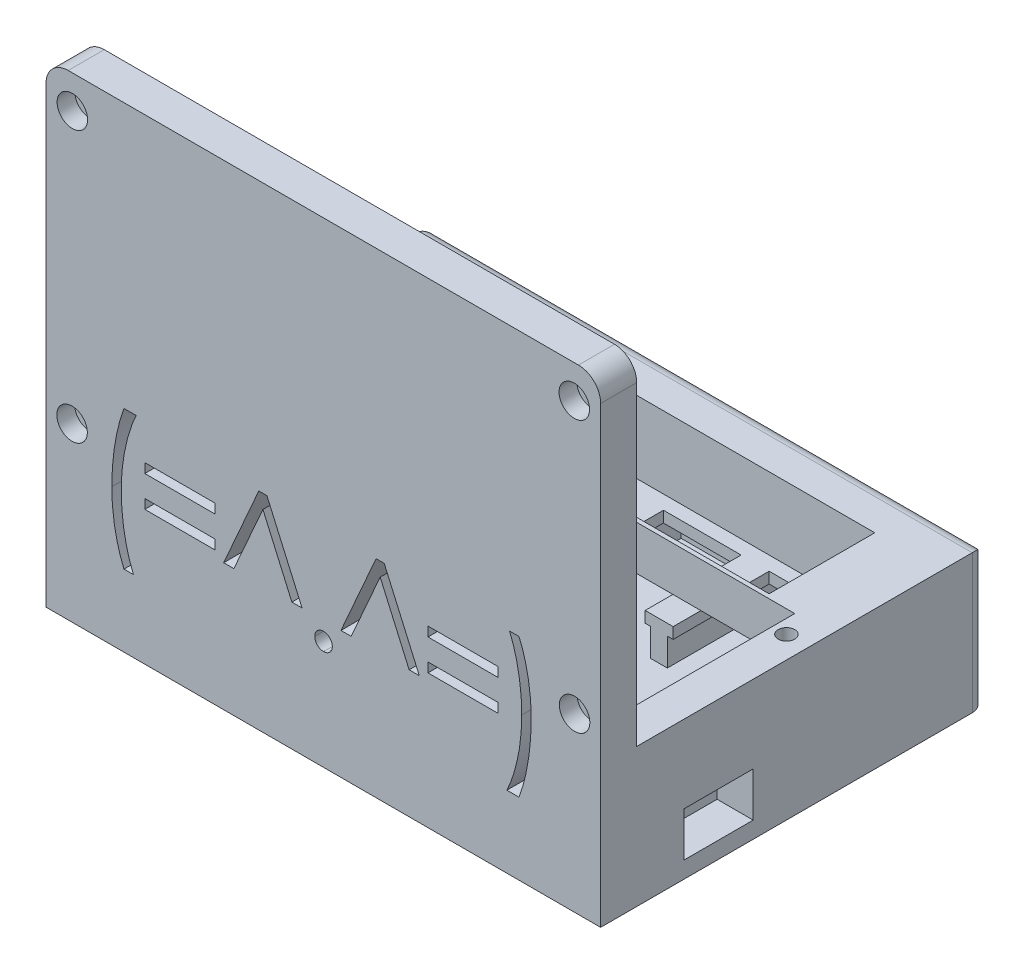
SolidWorks part; units mm, degrees
note: The reader was unsure of these and kept them because the rebuilt part matched: shared geometry of "Sketch32<3>".
ref_plane "Front Plane" through (0, 0, 0) normal (0, 0, 1) x (1, 0, 0)
ref_plane "Top Plane" through (0, 0, 0) normal (0, 1, 0) x (1, 0, 0)
ref_plane "Right Plane" through (0, 0, 0) normal (1, 0, 0) x (0, 0, -1)
sketch "Sketch1" plane through (0, 0, 0) normal (1, 0, 0) x (0, 0, -1)
  line L0 (-31.5, 12.5) -> (-31.5, 73.3)
  line L1 (-31.5, -12.5) -> (31.5, -12.5)
  line L2 (-31.5, -12.5) -> (-31.5, 12.5) construction
  line L3 (-31.5, 12.5) -> (31.5, 12.5)
  line L4 (31.5, -12.5) -> (31.5, 12.5)
  line L5 (-31.5, -12.5) -> (31.5, 12.5) construction
  line L6 (-31.5, 12.5) -> (31.5, -12.5) construction
  line L7 (-31.5, -12.5) -> (-38, -12.5)
  line L8 (-31.5, -12.5) -> (-31.5, 73.3) construction
  line L9 (-31.5, 73.3) -> (-38, 73.3)
  line L10 (-38, -12.5) -> (-38, 73.3)
  point P0 (0, 0)
  dimension "D1" = 25
  dimension "D2" = 63
  dimension "D3" = 6.5
  dimension "D4" = 60.8
extrude "Boss-Extrude1" add sketch "Sketch1" along normal blind 100
shell "Shell1" thickness 6.5
sketch "Sketch3" plane through (0, 0, 31.5) normal (0, 0, -1) x (-1, 0, 0)
  line L0 (-100, 12.5) -> (-100, 73.3) construction
  line L1 (-100, 12.5) -> (0, 12.5) construction
  line L2 (-50, 73.3) -> (-50, 12.5) construction
  line L3 (-100, 73.3) -> (0, 73.3) construction
  circle A0 centre (-95.3, 18.5) radius 1.25
  circle A1 centre (-4.7, 18.5) radius 1.25
  circle A2 centre (-95.25, 67.3533) radius 1.25
  circle A3 centre (-4.75, 67.3533) radius 1.25
  dimension "D1" = 2.5
  dimension "D4" = 2.5
  dimension "D5" = 2.5
  dimension "D2" = 4.7
  dimension "D3" = 6
extrude "Cut-Extrude1" cut sketch "Sketch3" against normal up to surface (6.5 mm away) up to face at (50, 30.4, 38)
sketch "Sketch4" plane through (0, 12.5, 0) normal (0, 1, 0) x (1, 0, 0)
  circle A0 centre (4, -0.5) radius 1.5
  circle A1 centre (96, -0.5) radius 1.5
  dimension "D1" = 3
  dimension "D2" = 3
extrude "Cut-Extrude2" cut sketch "Sketch4" against normal up to surface (25 mm away) contours A1 | A0 up to face at (50, -12.5, 3.25)
fillet "Fillet1" radius 2.5 3 edges at (100, 0, -31.5) (0, 0, -31.5) (50, 12.5, -31.5)
sketch "Sketch5" plane through (0, 0, 38) normal (0, 0, 1) x (1, 0, 0)
  line L0 (50, -12.5) -> (50, 73.3) construction
  line L6 (100, -12.5) -> (0, -12.5) construction
  line L7 (100, 73.3) -> (0, 73.3) construction
  text T0 "(=^.^=)" font "Century Gothic" height 19
  dimension "D1" = 41.3
extrude "Cut-Extrude3" cut sketch "Sketch5" against normal up to surface (6.5 mm away)
fillet "Fillet2" radius 4 2 edges at (0, 73.3, 34.75) (100, 73.3, 34.75)
sketch "Sketch26" plane through (0, 0, 31.5) normal (0, 0, -1) x (-1, 0, 0)
  line L0 (-93.5, -6) -> (-6.5, -6) construction
  line L1 (-93.5, -6) -> (-6.5, -6)
  line L2 (-93.5, -6) -> (-93.5, -7.5)
  line L3 (-93.5, -7.5) -> (-6.5, -7.5)
  line L4 (-6.5, -6) -> (-6.5, -7.5)
  line L5 (-93.5, -6) -> (-6.5, -6)
  dimension "D1" = 1.5
extrude "Cut-Extrude15" cut sketch "Sketch26" along normal up to surface (56.5 mm away) contours L4 L1 L2 L3 up to face at (50, 3.25, -25)
sketch "Sketch19" plane through (0, 0, -25) normal (0, 0, 1) x (1, 0, 0)
  line L0 (6.5, -7.5) -> (6.5, 12.5) construction
  line L1 (6.5, -2.5) -> (10.46, -2.5)
  line L2 (6.5, -2.5) -> (6.5, -0.5)
  line L3 (6.5, -0.5) -> (93.5, -0.5)
  line L4 (93.5, -2.5) -> (93.5, -0.5)
  line L5 (93.5, -7.5) -> (93.5, 12.5) construction
  line L6 (93.5, 12.5) -> (6.5, 12.5) construction
  line L9 (10.46, -2.5) -> (10.46, -7.5)
  line L11 (13.46, -2.5) -> (13.46, -7.5)
  line L12 (93.5, -7.5) -> (6.5, -7.5)
  line L13 (29.48, -2.5) -> (29.48, -7.5)
  line L14 (32.48, -2.5) -> (32.48, -7.5)
  line L15 (48.5, -2.5) -> (48.5, -7.5)
  line L16 (51.5, -2.5) -> (51.5, -7.5)
  line L17 (67.52, -2.5) -> (67.52, -7.5)
  line L18 (70.52, -2.5) -> (70.52, -7.5)
  line L19 (86.54, -2.5) -> (86.54, -7.5)
  line L20 (89.54, -2.5) -> (89.54, -7.5)
  line L21 (13.46, -2.5) -> (29.48, -2.5) construction
  line L22 (48.5, -5) -> (51.5, -5) construction
  line L23 (50, -2.5) -> (50, -7.5) construction
  line L24 (13.46, -2.5) -> (29.48, -2.5)
  line L25 (32.48, -2.5) -> (48.5, -2.5)
  line L26 (51.5, -2.5) -> (67.52, -2.5)
  line L27 (70.52, -2.5) -> (86.54, -2.5)
  line L28 (89.54, -2.5) -> (93.5, -2.5)
  line L31 (93.5, -7.5) -> (6.5, -7.5) construction
  point P37 (50, -5)
  dimension "D1" = 13
  dimension "D2" = 2
  dimension "D3" = 3
  dimension "D5" = 19.02
  dimension "D4" = 5
extrude "Boss-Extrude5" add sketch "Sketch19" along normal blind 21.5
sketch "Sketch20" plane through (0, -0.5, 0) normal (0, 1, 0) x (1, 0, 0)
  line L0 (6.5, 3.5) -> (93.5, 3.5) construction
  line L1 (14.425, 20.8) -> (28.425, 20.8)
  line L2 (14.425, 20.8) -> (14.425, 6.8)
  line L4 (28.425, 20.8) -> (28.425, 6.8)
  line L5 (33.475, 20.8) -> (47.475, 20.8)
  line L6 (33.475, 20.8) -> (33.475, 6.8)
  line L8 (47.475, 20.8) -> (47.475, 6.8)
  line L9 (52.525, 20.8) -> (66.525, 20.8)
  line L10 (52.525, 20.8) -> (52.525, 6.8)
  line L12 (66.525, 20.8) -> (66.525, 6.8)
  line L13 (71.575, 20.8) -> (85.575, 20.8)
  line L14 (71.575, 20.8) -> (71.575, 6.8)
  line L16 (85.575, 20.8) -> (85.575, 6.8)
  line L17 (14.425, 20.8) -> (33.475, 20.8) construction
  line L18 (47.475, 13.8) -> (52.525, 13.8) construction
  line L19 (6.5, 25) -> (93.5, 25) construction
  line L22 (14.425, 6.8) -> (14.425, 3.5)
  line L23 (14.425, 3.5) -> (28.425, 3.5)
  line L24 (28.425, 6.8) -> (28.425, 3.5)
  line L26 (33.475, 6.8) -> (33.475, 3.5)
  line L27 (33.475, 3.5) -> (47.475, 3.5)
  line L28 (47.475, 6.8) -> (47.475, 3.5)
  line L30 (52.525, 6.8) -> (52.525, 3.5)
  line L31 (52.525, 3.5) -> (66.525, 3.5)
  line L32 (66.525, 6.8) -> (66.525, 3.5)
  line L34 (71.575, 6.8) -> (71.575, 3.5)
  line L35 (71.575, 3.5) -> (85.575, 3.5)
  line L36 (85.575, 6.8) -> (85.575, 3.5)
  point P24 (50, 25)
  point P25 (50, 13.8)
  dimension "D1" = 14
  dimension "D2" = 17.3
  dimension "D4" = 19.05
  dimension "D3" = 4
extrude "Cut-Extrude11" cut sketch "Sketch20" against normal up to next
sketch "Sketch21" plane through (0, -0.5, 0) normal (0, 1, 0) x (1, 0, 0)
  line L0 (30.95, 4.275) -> (50, 4.275)
  line L1 (11.9, 4.275) -> (30.95, 4.275)
  line L2 (11.9, 4.275) -> (11.9, 23.325)
  line L3 (11.9, 23.325) -> (30.95, 23.325)
  line L4 (30.95, 4.275) -> (30.95, 23.325)
  line L5 (11.9, 4.275) -> (30.95, 23.325) construction
  line L6 (11.9, 23.325) -> (30.95, 4.275) construction
  line L7 (30.95, 4.275) -> (30.95, 23.325)
  line L8 (30.95, 23.325) -> (50, 23.325)
  line L9 (50, 4.275) -> (50, 23.325)
  line L10 (50, 4.275) -> (69.05, 4.275)
  line L11 (50, 4.275) -> (50, 23.325)
  line L12 (50, 23.325) -> (69.05, 23.325)
  line L13 (69.05, 4.275) -> (69.05, 23.325)
  line L14 (69.05, 4.275) -> (88.1, 4.275)
  line L15 (69.05, 4.275) -> (69.05, 23.325)
  line L16 (69.05, 23.325) -> (88.1, 23.325)
  line L17 (88.1, 4.275) -> (88.1, 23.325)
  line L18 (11.9, 4.275) -> (30.95, 4.275) construction
  line L19 (93.5, 3.5) -> (93.5, 25) construction
  line L20 (6.5, 25) -> (93.5, 25) construction
  line L22 (6.5, 3.5) -> (6.5, 25) construction
  line L23 (93.5, 3.5) -> (93.5, 25)
  line L24 (6.5, 25) -> (93.5, 25)
  line L25 (6.5, 3.5) -> (93.5, 3.5)
  line L26 (6.5, 3.5) -> (6.5, 25)
  point P0 (21.425, 13.8)
  line M20 (93.5, 25) -> (6.5, 25)
  line M21 (6.5, 25) -> (6.5, 3.5)
  line M22 (6.5, 3.5) -> (14.425, 3.5)
  line M23 (93.5, 3.5) -> (93.5, 25)
  dimension "D1" = 19.05
  dimension "D3" = 19.05
  dimension "D4" = 87
  dimension "D2" = 4
extrude "Boss-Extrude6" add sketch "Sketch21" along normal up to surface (13 mm away) contours L17 L14 L10 L0 L1 L2 L3 L8 L12 L16 M23 M20 M21 M22 up to face at (96, 12.5, 2)
sketch "Sketch23" plane through (0, -12.5, 0) normal (0, -1, 0) x (1, 0, 0)
  circle A0 centre (4, 0.5) radius 2.75
  circle A1 centre (96, 0.5) radius 2.75
  dimension "D1" = 5.5
  dimension "D2" = 5.5
extrude "Cut-Extrude12" cut sketch "Sketch23" against normal blind 3.2
sketch "Sketch24" plane through (100, 0, 0) normal (1, 0, 0) x (0, 0, -1)
  line L0 (-31.5, 12.5) -> (-31.5, 69.3) construction
  line L1 (-21.5, -3.5) -> (-12, -3.5)
  line L2 (-21.5, -3.5) -> (-21.5, -7.5)
  line L3 (-21.5, -7.5) -> (-12, -7.5)
  line L4 (-12, -3.5) -> (-12, -7.5)
  line L5 (-21.5, -3.5) -> (-12, -7.5) construction
  line L6 (-21.5, -7.5) -> (-12, -3.5) construction
  line L7 (3.5, -7.5) -> (25, -7.5) construction
  line L9 (-23, -9.5) -> (-10.5, -9.5)
  line L10 (-23, -9.5) -> (-23, -1.5)
  line L11 (-23, -1.5) -> (-10.5, -1.5)
  line L12 (-10.5, -9.5) -> (-10.5, -1.5)
  line L13 (-23, -9.5) -> (-10.5, -1.5) construction
  line L14 (-23, -1.5) -> (-10.5, -9.5) construction
  point P0 (-16.75, -5.5)
  point P7 (-16.75, -5.5)
  dimension "D1" = 4
  dimension "D2" = 9.5
  dimension "D3" = 10
  dimension "D4" = 8
  dimension "D5" = 12.5
extrude "Cut-Extrude13" cut sketch "Sketch24" against normal up to vertex (6.5 mm away) contours L4 L1 L2 L3 | L9 L12 L11 L10 L1 L4 L3 L2
sketch "Sketch25" plane through (0, 0, 38) normal (0, 0, 1) x (1, 0, 0)
  circle A0 centre (4.75, 67.3533) radius 2.75
  circle A1 centre (4.7, 18.5) radius 2.75
  circle A2 centre (95.3, 18.5) radius 2.75
  circle A3 centre (95.25, 67.3533) radius 2.75
  dimension "D1" = 5.5
  dimension "D2" = 5.5
  dimension "D3" = 5.5
  dimension "D4" = 5.5
extrude "Cut-Extrude14" cut sketch "Sketch25" against normal blind 3.2
sketch "Sketch28" plane through (14.425, 0, 0) normal (1, 0, 0) x (0, 0, -1)
  line L0 (4.275, 12.5) -> (4.275, -0.5) construction
  line L1 (3.5, 12.5) -> (4.275, 12.5)
  line L2 (3.5, 12.5) -> (3.5, 4.5)
  line L3 (3.5, 4.5) -> (4.275, 4.5)
  line L4 (4.275, 12.5) -> (4.275, 4.5)
  dimension "D1" = 8
extrude "Boss-Extrude7" add sketch "Sketch28" along normal up to surface (71.15 mm away) up to face at (85.575, 3.1667, -9.525)
sketch "Sketch30" plane through (0, -7.5, 0) normal (0, 1, 0) x (1, 0, 0)
  text T0 "Tuomaa 260402" font "Century Gothic" height in points 10
extrude "Cut-Extrude16" cut sketch "Sketch30" against normal blind 1
sketch "Sketch32" plane through (0, -7.5, 0) normal (0, -1, 0) x (-1, 0, 0)
  line L0 (-91.5, -5) -> (-91.5, -28.5) construction
  line L1 (-91.5, -28.5) -> (-91.5, -16.75) construction
  line L2 (-91.5, -16.75) -> (99.0754, -16.75) construction
  line L3 (-93.5, -10.5) -> (-93.5, -23) construction
  line L4 (-93.5, 25) -> (-93.5, -10.5) construction
  line L5 (-93.5, 25) -> (-93.5, -10.5) construction
  line L7 (-67.845, -16.75) -> (-67.845, -29.4963) construction
  circle A0 centre (-91.5, -5) radius 1.25
  circle A1 centre (-91.5, -28.5) radius 1.25
  circle A2 centre (-91.5, -5) radius 2.5
  circle A3 centre (-91.5, -28.5) radius 2.5
  circle A4 centre (-44.19, -28.5) radius 1.25
  circle A5 centre (-44.19, -28.5) radius 2.5
  circle A6 centre (-44.19, -5) radius 1.25
  circle A7 centre (-44.19, -5) radius 2.5
  point P11 (-93.5, -16.75)
  dimension "D1" = 2.5
  dimension "D2" = 2.5
  dimension "D3" = 23.5
  dimension "D5" = 5
  dimension "D6" = 5
  dimension "D4" = 2
  dimension "D7" = 25.655
extrude "Boss-Extrude10" add sketch "Sketch32" against normal blind 3.6
extrude "Cut-Extrude18" cut sketch "Sketch32<3>" along normal through all contours A0 | A1 | A6 | A4
sketch "Sketch32<3>" plane through (0, -7.5, 0) normal (0, -1, 0) x (-1, 0, 0) same geometry as "Sketch32"
sketch "Sketch33" plane through (100, 0, 0) normal (1, 0, 0) x (0, 0, -1)
  line L1 (-23, -9.5) -> (-10.5, -9.5)
  line L2 (-23, -9.5) -> (-23, -1.5)
  line L3 (-23, -1.5) -> (-10.5, -1.5)
  line L4 (-10.5, -9.5) -> (-10.5, -1.5)
  line L5 (-21.5, -3.5) -> (-21.5, -7.5) construction
  line L6 (-12, -7.5) -> (-12, -3.5) construction
  line L7 (-21.5, -7.5) -> (-12, -7.5) construction
  line L8 (-12, -3.5) -> (-21.5, -3.5) construction
  dimension "D1" = 1.5
  dimension "D2" = 1.5
  dimension "D3" = 2
  dimension "D4" = 2
ref_plane "Plane2" through (0, 0, -3.5) normal (0, 0, 1) x (1, 0, 0)
